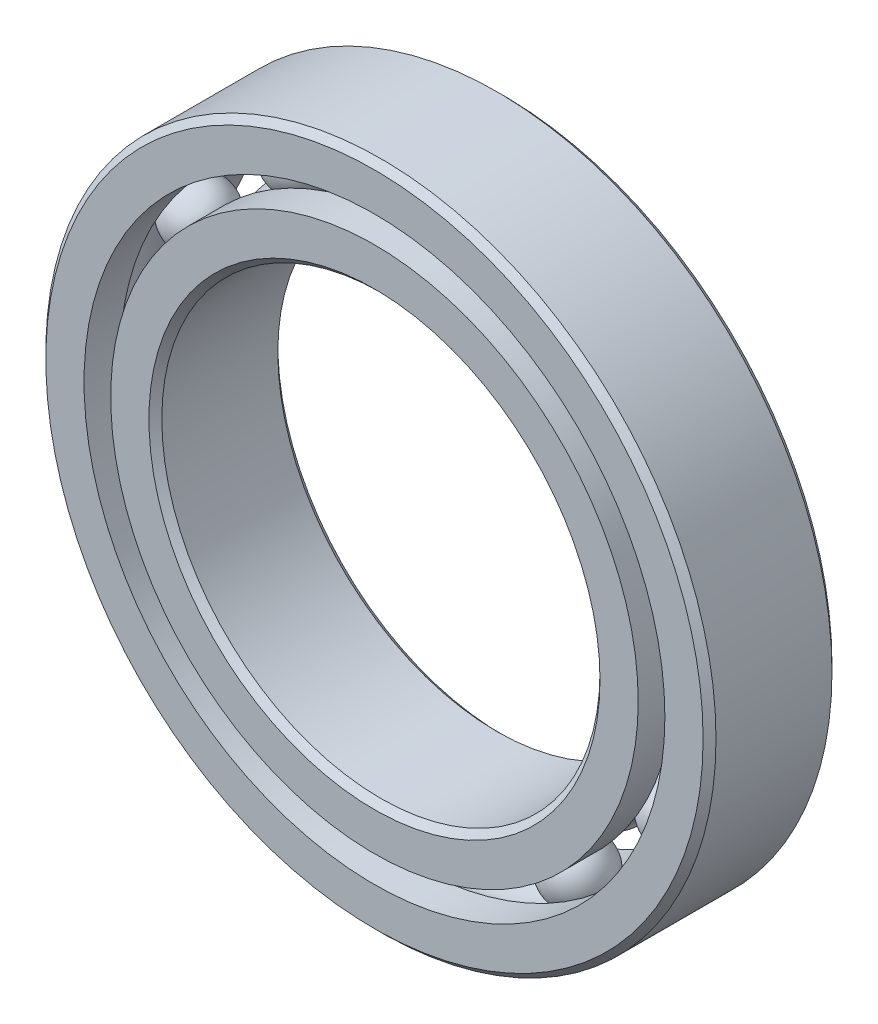
SolidWorks part; units mm, degrees
ref_plane "Front Plane" through (0, 0, 0) normal (0, 0, 1) x (1, 0, 0)
ref_plane "Top Plane" through (0, 0, 0) normal (0, 1, 0) x (1, 0, 0)
ref_plane "Right Plane" through (0, 0, 0) normal (1, 0, 0) x (0, 0, -1)
sketch "Sketch1" plane through (0, 0, 0) normal (1, 0, 0) x (0, 0, -1)
  line L0 (-2.5, 0) -> (2.5, 0) construction
  line L1 (0, 13) -> (0, -13) construction
  line L2 (2.25, 13) -> (-2.25, 13)
  line L3 (-2.25, 13) -> (-2.5, 12.75)
  line L4 (-2.5, 12.75) -> (-2.5, 11.2674)
  line L5 (-2.5, 11.2674) -> (-1.1111, 11.2674)
  line L6 (2.5, 11.2674) -> (1.1111, 11.2674)
  line L7 (2.5, 12.75) -> (2.5, 11.2674)
  line L8 (2.25, 13) -> (2.5, 12.75)
  line L9 (0, 13) -> (0, 10.75) construction
  line L10 (0, 10.75) -> (0, 8.5) construction
  arc A0 (-1.1111, 11.2674) -> (1.1111, 11.2674) centre (0, 10.75) cw
  point P14 (0, 8.5)
  dimension "Width" = 5
  dimension "OD" = 26
  dimension "D1" = 45
  dimension "D2" = 0.25
  dimension "Shaft Dia" = 17
  dimension "D3" = 2.2222
revolve "Revolve1" add sketch "Sketch1" angle 360 about L0
sketch "Sketch3" plane through (0, 0, 0) normal (1, 0, 0) x (0, 0, -1)
  line L0 (-2.5, 10.2326) -> (-1.1111, 10.2326)
  line L1 (0, 13) -> (0, -13) construction
  line L2 (-2.5, 12.75) -> (-2.5, 11.2674) construction
  line L3 (-2.5, 10.2326) -> (-2.5, 8.75)
  line L4 (-2.25, 13) -> (-2.5, 12.75) construction
  line L5 (-2.5, 8.75) -> (-2.25, 8.5)
  line L6 (-2.25, 8.5) -> (2.25, 8.5)
  line L7 (2.25, 13) -> (2.25, -13) construction
  line L8 (2.25, 8.5) -> (2.5, 8.75)
  line L9 (2.5, -12.75) -> (2.5, 12.75) construction
  line L10 (2.5, 8.75) -> (2.5, 10.2326)
  line L11 (2.5, 10.2326) -> (1.1111, 10.2326)
  line L13 (2.25, 13) -> (2.5, 12.75) construction
  arc A0 (1.1111, 11.2674) -> (-1.1111, 11.2674) centre (0, 10.75) ccw construction
  arc A1 (1.1111, 10.2326) -> (-1.1111, 10.2326) centre (0, 10.75) cw
revolve "Revolve3" add sketch "Sketch3" angle 360 about L0
sketch "Sketch4" plane through (0, 0, 0) normal (1, 0, 0) x (0, 0, -1)
  line L0 (-1.2257, 10.75) -> (1.2257, 10.75)
  arc A2 (-1.2257, 10.75) -> (1.2257, 10.75) centre (0, 10.75) cw
  arc A3 (1.1111, 11.2674) -> (-1.1111, 11.2674) centre (0, 10.75) ccw construction
revolve "Revolve4" add sketch "Sketch4" angle 360 about L0
ref_axis "Axis1" through (0, 0, -2.5) along (0, 0, 1)
pattern_circular "CirPattern1" count 12 every 30 about axis through (0, 0, -2.5) along (0, 0, 1) of bodies 104
sketch "Sketch5" plane through (0, 0, 0) normal (1, 0, 0) x (0, 0, -1)
  line L0 (-2.5, 11.2674) -> (-1.1111, 11.2674) construction
  line L1 (-2.375, 11.2674) -> (-1.2257, 11.2674)
  line L2 (-2.375, 11.2674) -> (-2.375, 10.2326)
  line L3 (-2.375, 10.2326) -> (-1.2257, 10.2326)
  line L4 (-1.2257, 11.2674) -> (-1.2257, 10.2326)
  line L5 (-2.5, 10.2326) -> (-1.1111, 10.2326) construction
  line L6 (2.5, 11.2674) -> (1.1111, 11.2674) construction
  line L7 (2.375, 11.2674) -> (1.2257, 11.2674)
  line L8 (2.375, 11.2674) -> (2.375, 10.2326)
  line L9 (2.375, 10.2326) -> (1.2257, 10.2326)
  line L10 (1.2257, 11.2674) -> (1.2257, 10.2326)
  line L11 (2.5, 10.2326) -> (1.1111, 10.2326) construction
  line L12 (-2.25, 13) -> (-2.5, 12.75) construction
  point P18 (-2.375, 12.875)
equation "\"D2@Sketch1\" = \"Width@Sketch1\"*.05"
equation "\"D3@Sketch1\" = \"Width@Sketch1\"/2.25"
equation "\"D2@CirPattern1\" = 360/\"Balls@CirPattern1\""
